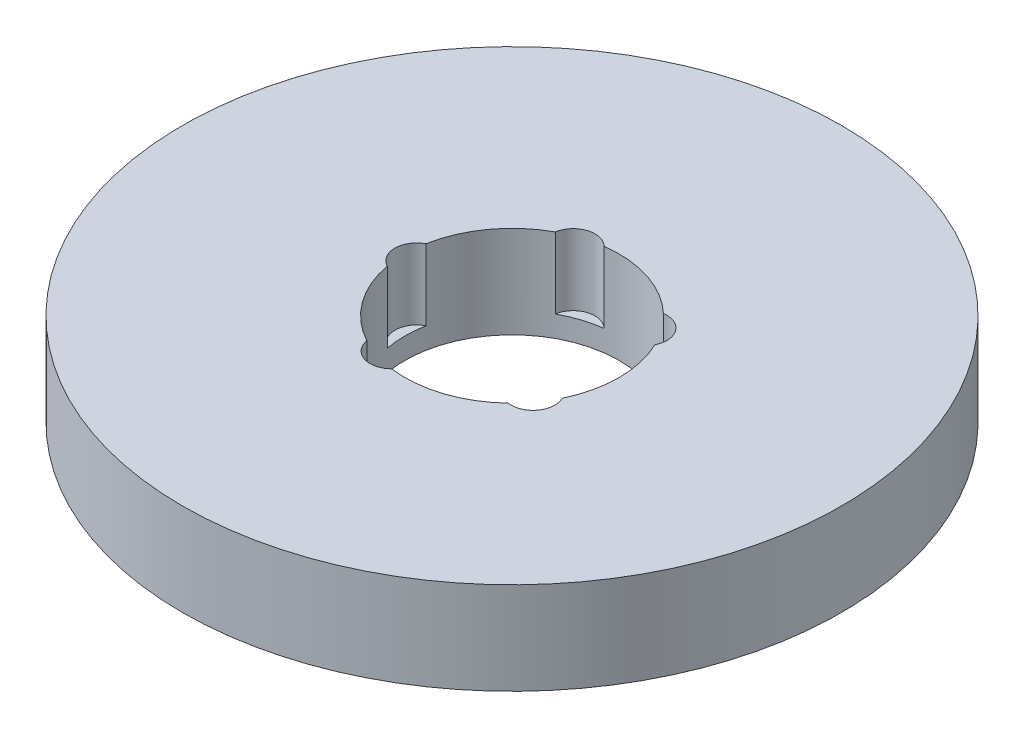
SolidWorks part; units mm, degrees
ref_plane "Front Plane" through (0, 0, 0) normal (0, 0, 1) x (1, 0, 0)
ref_plane "Top Plane" through (0, 0, 0) normal (0, 1, 0) x (1, 0, 0)
ref_plane "Right Plane" through (0, 0, 0) normal (1, 0, 0) x (0, 0, -1)
sketch "Sketch1" plane through (0, 0, 0) normal (0, 1, 0) x (1, 0, 0)
  circle A0 centre (0, 0) radius 100
  dimension "FLANGE_OD" = 200
extrude "Boss-Extrude1" add sketch "Sketch1" along normal blind 28
sketch "Sketch2" plane through (0, 0, 0) normal (0, 1, 0) x (1, 0, 0)
  circle A0 centre (0, 0) radius 32.5
  dimension "BORE_D" = 65
extrude "Cut-Extrude1" cut sketch "Sketch2" along normal through all
sketch "Sketch3" plane through (0, 28, 0) normal (0, 1, 0) x (1, 0, 0)
  circle A0 centre (0, 0) radius 28.9135 construction
  circle A1 centre (-28.9135, 0) radius 6.6156
  dimension "BOLT_D" = 13.2312
  dimension "BOLT_PCD" = 57.8269
extrude "Cut-Extrude2" cut sketch "Sketch3" against normal blind 21.5632
pattern_circular "CirPattern1" count 5 over 360 about axis through (0, 0, 0) along (0, 1, 0) of "Cut-Extrude2"
